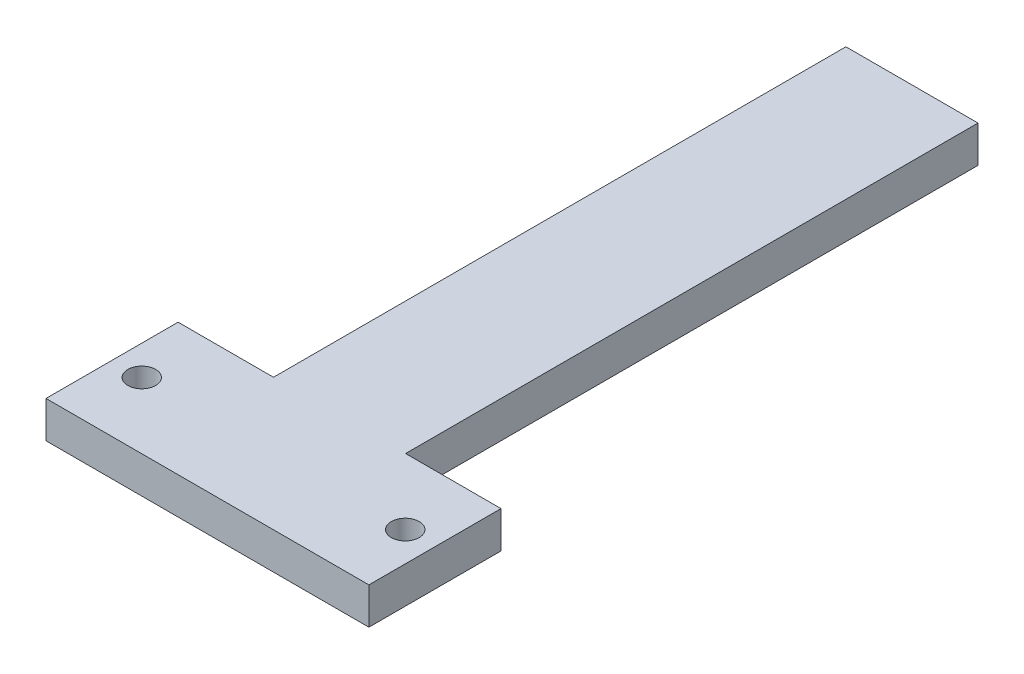
SolidWorks part; units mm, degrees
ref_plane "Front Plane" through (0, 0, 0) normal (0, 0, 1) x (1, 0, 0)
ref_plane "Top Plane" through (0, 0, 0) normal (0, 1, 0) x (1, 0, 0)
ref_plane "Right Plane" through (0, 0, 0) normal (1, 0, 0) x (0, 0, -1)
sketch "Sketch1" plane through (0, 0, 0) normal (0, 1, 0) x (1, 0, 0)
  line L1 (27.94, -11.43) -> (-27.94, -11.43)
  line L2 (27.94, -11.43) -> (27.94, 11.43)
  line L3 (27.94, 11.43) -> (-27.94, 11.43)
  line L4 (-27.94, -11.43) -> (-27.94, 11.43)
  line L5 (27.94, -11.43) -> (-27.94, 11.43) construction
  line L6 (27.94, 11.43) -> (-27.94, -11.43) construction
  line L7 (0, 11.43) -> (-11.43, 11.43)
  line L8 (0, 11.43) -> (0, 110.49)
  line L9 (0, 110.49) -> (-11.43, 110.49)
  line L10 (-11.43, 11.43) -> (-11.43, 110.49)
  line L11 (0, 11.43) -> (11.43, 11.43)
  line L12 (0, 11.43) -> (0, 110.49)
  line L13 (0, 110.49) -> (11.43, 110.49)
  line L14 (11.43, 11.43) -> (11.43, 110.49)
  circle A0 centre (-22.7965, 0) radius 2.413
  circle A1 centre (22.7965, 0) radius 2.413
  point P0 (0, 0)
  dimension "D6" = 4.826
  dimension "D7" = 4.826
  dimension "D8" = 45.593
  dimension "D9" = 22.7965
  dimension "D1" = 22.86
  dimension "D2" = 55.88
  dimension "D3" = 11.43
  dimension "D4" = 11.43
  dimension "D5" = 99.06
extrude "Boss-Extrude1" add sketch "Sketch1" along normal blind 6.35 contours L3 L14 L13 L8 | L10 L3 L8 L9 | L4 L1 L2 L3 A1 A0 region at (0, 0, 0) region at (5.715, 0, -60.96) region at (-5.715, 0, -60.96)
